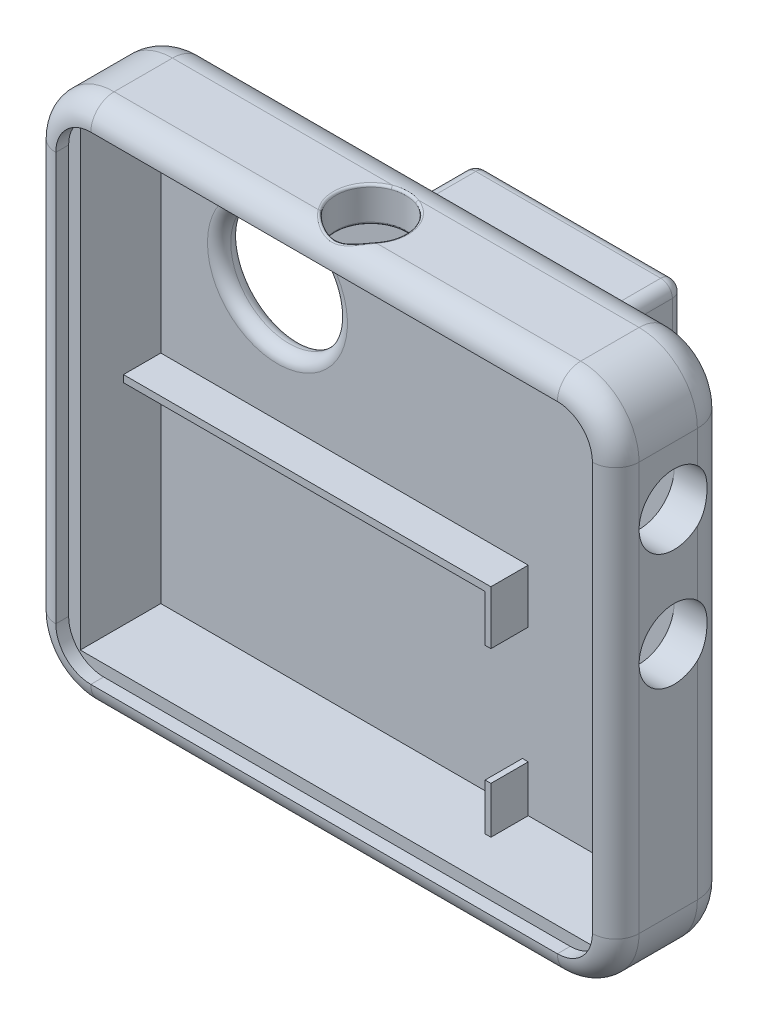
SolidWorks part; units mm, degrees
material "Latão de corte livre, UNS C36000"
ref_plane "Plano frontal" through (0, 0, 0) normal (0, 0, 1) x (1, 0, 0)
ref_plane "Plano superior" through (0, 0, 0) normal (0, 1, 0) x (1, 0, 0)
ref_plane "Plano direito" through (0, 0, 0) normal (1, 0, 0) x (0, 0, -1)
sketch "Esboço1" plane through (0, 0, 0) normal (0, 0, 1) x (1, 0, 0)
  line L1 (-20, 22.5) -> (30, 22.5)
  line L2 (-20, 22.5) -> (-20, -22.5)
  line L3 (-20, -22.5) -> (30, -22.5)
  line L4 (30, 22.5) -> (30, -22.5)
  dimension "D1" = 45
  dimension "D2" = 50
extrude "Ressalto-extrusão1" add sketch "Esboço1" along normal blind 10
fillet "Filete1" radius 5 4 edges at (-20, 22.5, 5) (-20, -22.5, 5) (30, -22.5, 5) (30, 22.5, 5)
fillet "Filete2" radius 3 8 edges at (30, 0, 0) (28.5355, 21.0355, 0) (28.5355, -21.0355, 0) (-18.5355, -21.0355, 0) (5, -22.5, 0) (-20, 0, 0) (-18.5355, 21.0355, 0) (5, 22.5, 0)
fillet "Filete3" radius 2 8 edges at (-18.5355, -21.0355, 10) (-20, 0, 10) (-18.5355, 21.0355, 10) (28.5355, -21.0355, 10) (5, -22.5, 10) (30, 0, 10) (28.5355, 21.0355, 10) (5, 22.5, 10)
sketch "Esboço2" plane through (0, 0, 10) normal (0, 0, 1) x (1, 0, 0)
  line L2 (-17, 19.5) -> (27, 19.5)
  line L4 (27, 19.5) -> (27, -19.5)
  line L6 (27, -19.5) -> (-17, -19.5)
  line L8 (-17, -19.5) -> (-17, 19.5)
  line L9 (25, 20.5) -> (-15, 20.5) construction
  line L10 (-15, -20.5) -> (25, -20.5) construction
  line L11 (28, -17.5) -> (28, 17.5) construction
  line L12 (-18, 17.5) -> (-18, -17.5) construction
  dimension "D1" = 1
  dimension "D2" = 1
  dimension "D3" = 1
  dimension "D4" = 1
extrude "Corte-extrusão1" cut sketch "Esboço2" against normal blind 8
sketch "Esboço3" plane through (0, 0, 2) normal (0, 0, 1) x (1, 0, 0)
  line L1 (-17, 19.5) -> (-17, -19.5) construction
  line L2 (-17, -0.9003) -> (-17, -1.5)
  line L3 (14, -19.5) -> (14, -1.5)
  line L4 (14, -1.5) -> (14, -19.5) construction
  line L6 (-17, -19.5) -> (27, -19.5) construction
  line L8 (14, -19.5) -> (14.4994, -19.5)
  line L11 (14.4994, -19.5) -> (14, -19.5)
  line L12 (14, -1.5) -> (-17, -1.5)
  line L13 (-17, -1.5) -> (-17, -0.9003)
  line L14 (-17, -0.9003) -> (14.4994, -0.9003)
  line L15 (14.4994, -0.9003) -> (14.4994, -19.5)
  line M7 (-17, 19.5) -> (-17, -19.5)
  line M8 (-17, -19.5) -> (27, -19.5)
  dimension "D1" = 18
extrude "Ressalto-extrusão3" add sketch "Esboço3" along normal blind 3.2 contours L15 L14 L12 L3 M7 M8 region at (-1.2503, -1.2661, 2)
sketch "Esboço5" plane through (14, 0, 0) normal (-1, 0, 0) x (0, 0, 1)
  line L0 (7, -5.5) -> (7, -15.5)
  line L7 (2, -1.5) -> (2, -19.5) construction
  line L8 (2, -5.5) -> (7, -5.5)
  line L10 (7, -15.5) -> (2, -15.5)
  line L11 (2, -15.5) -> (2, -5.5)
  dimension "D1" = 5
extrude "Corte-extrusão2" cut sketch "Esboço5" against normal blind 3.2
sketch "Esboço6" plane through (0, 0, 2) normal (0, 0, 1) x (1, 0, 0)
  line L0 (-17, 9.2999) -> (-7, 9.2999) construction
  line L3 (-17, 19.5) -> (-17, -0.9003) construction
  circle A0 centre (-7, 9.2999) radius 5
  dimension "D1" = 10
  dimension "D2" = 10
extrude "Corte-extrusão3" cut sketch "Esboço6" against normal blind 3.2
fillet "Filete4" radius 1 2 edges at (-2, 9.2999, 2) (-2, 9.2999, 0)
sketch "Esboço7" plane through (30, 0, 0) normal (1, 0, 0) x (0, 0, -1)
  circle A1 centre (-5, 2.5) radius 3
  circle A2 centre (-5, 12.5) radius 3
extrude "Corte-extrusão4" cut sketch "Esboço7" against normal blind 3.2
sketch "Esboço8" plane through (0, 19.5, 0) normal (0, -1, 0) x (1, 0, 0)
  circle A0 centre (5, 6) radius 3
  dimension "D1" = 6
extrude "Corte-extrusão5" cut sketch "Esboço8" against normal blind 3.2
fillet "Filete7" radius 0.2 4 edges at (5, 19.5, 3) (7.7386, 22.5, 4.7753) (5.4192, 22.2487, 8.9706) (2.2614, 22.5, 4.7753)
sketch "Esboço11" plane through (0, 0, 10) normal (0, 0, 1) x (1, 0, 0)
  line L0 (-18, 17.5) -> (-18, -17.5)
  line L2 (-15, -20.5) -> (25, -20.5)
  line L4 (28, -17.5) -> (28, 17.5)
  line L6 (25, 20.5) -> (-15, 20.5)
  arc A0 (-18, 17.5) -> (-15, 20.5) centre (-15, 17.5) cw
  arc A1 (25, 20.5) -> (28, 17.5) centre (25, 17.5) cw
  arc A2 (28, -17.5) -> (25, -20.5) centre (25, -17.5) cw
  arc A3 (-15, -20.5) -> (-18, -17.5) centre (-15, -17.5) cw
extrude "Corte-extrusão11" cut sketch "Esboço11" against normal blind 1.1
sketch "Esboço13" plane through (0, 0, 0) normal (0, 0, -1) x (-1, 0, 0)
  line L12 (-17.8542, 17.0816) -> (0, 17.0816)
  line L13 (0, 17.0816) -> (0, 12.0816)
  line L14 (0, 12.0816) -> (-17.8542, 12.0816)
  line L15 (-17.8542, 12.0816) -> (-17.8542, 17.0816)
  dimension "D1" = 5
extrude "Ressalto-extrusão5" add sketch "Esboço13" along normal blind 8
sketch "Esboço14" plane through (0, 12.0816, 0) normal (0, -1, 0) x (1, 0, 0)
  line L1 (0, -8) -> (0, 0) construction
  line L2 (0, -3) -> (17.8542, -3)
  line L3 (17.8542, -8) -> (17.8542, 0) construction
  line L6 (0, -3) -> (0, -8)
  line L7 (0, -8) -> (17.8542, -8)
  line L8 (17.8542, -8) -> (17.8542, -3)
  line L9 (17.8542, 0) -> (0, 0) construction
  dimension "D1" = 5
  dimension "D2" = 3
extrude "Ressalto-extrusão6" add sketch "Esboço14" along normal blind 20
fillet "Filete11" radius 1 13 edges at (0, 4.5816, -8) (17.8542, 4.5816, -8) (8.9271, 17.0816, -8) (0, 12.0816, -1.5) (17.8542, 12.0816, -1.5) (0, -7.9184, -5.5) (8.9271, -7.9184, -3) (17.8542, 2.0816, -3) (0, 2.0816, -3) (17.8542, -7.9184, -5.5) (8.9271, -7.9184, -8) (17.8542, 17.0816, -4) (0, 17.0816, -4)
